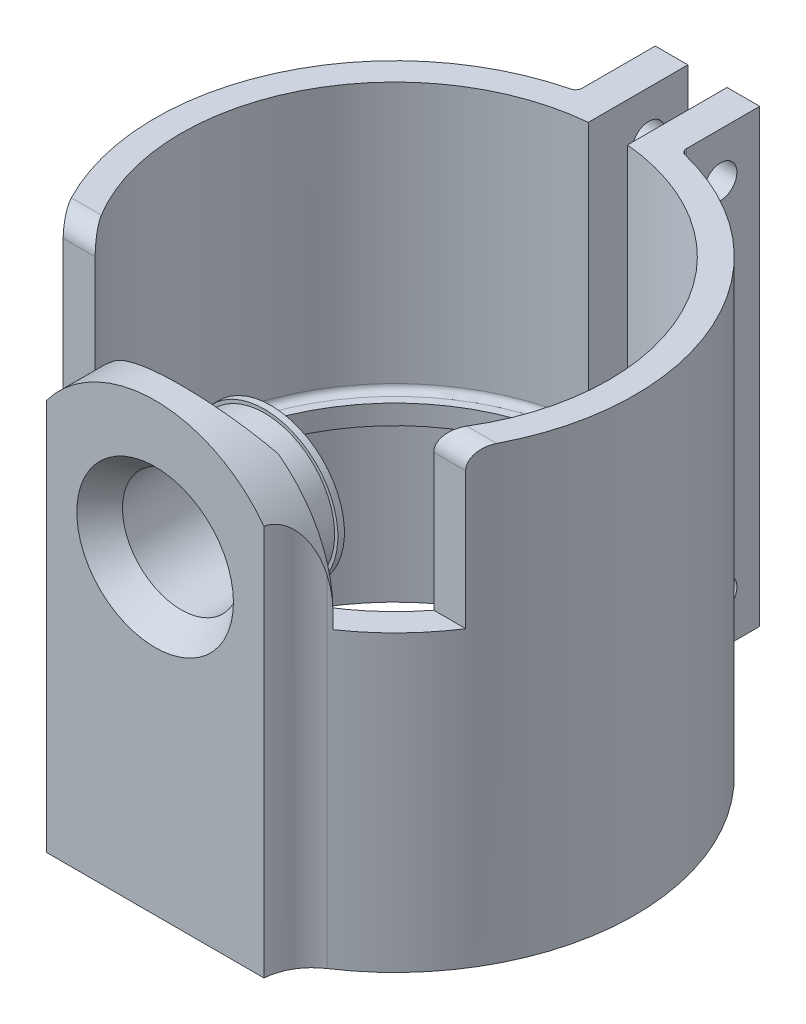
SolidWorks part; units mm, degrees
ref_plane "Спереди" through (0, 0, 0) normal (0, 0, 1) x (1, 0, 0)
ref_plane "Сверху" through (0, 0, 0) normal (0, 1, 0) x (1, 0, 0)
ref_plane "Справа" through (0, 0, 0) normal (1, 0, 0) x (0, 0, -1)
sketch "Эскиз1" plane through (0, 0, 0) normal (0, 1, 0) x (1, 0, 0)
  line L0 (0, 0) -> (0, -43.0119) construction
  line L2 (-16.6733, -36.75) -> (16.6733, -36.75)
  line L3 (-16.6733, -36.75) -> (-16.6733, -32.75)
  line L5 (16.6733, -36.75) -> (16.6733, -32.75)
  arc A0 (-16.6733, -32.75) -> (16.6733, -32.75) centre (0, 0) cw
  circle A1 centre (0, 0) radius 32.75
  dimension "D1" = 65.5
  dimension "D2" = 36.75
  dimension "D3" = 4
extrude "main" add sketch "Эскиз1" along normal blind 44 and the other way blind 25
sketch "Эскиз2" plane through (0, 0, 0) normal (0, 0, 1) x (1, 0, 0)
  circle A0 centre (0, 22.5) radius 11
  dimension "D1" = 22
  dimension "D2" = 22.5
extrude "hole" cut sketch "Эскиз2" along normal through all
sketch "Эскиз3" plane through (0, 0, 0) normal (0, 1, 0) x (1, 0, 0)
  circle A0 centre (0, 0) radius 32.75
  circle A1 centre (0, 0) radius 30.5
  circle A3 centre (0, 0) radius 32.75 construction
  dimension "D1" = 61
extrude "stop" add sketch "Эскиз3" along normal blind 3
sketch "Эскиз4" plane through (0, 0, 0) normal (0, 1, 0) x (1, 0, 0)
  line L0 (8, 35.8687) -> (0, 0) construction
  line L1 (0, 0) -> (-8, 35.8687) construction
  line L2 (0, 0) -> (0, 39.0687) construction
  line L3 (-8, 35.8687) -> (-8, 47.8687)
  line L4 (-8, 47.8687) -> (8, 47.8687)
  line L5 (8, 47.8687) -> (8, 35.8687)
  arc A0 (-8, 35.8687) -> (8, 35.8687) centre (0, 0) cw
  arc A1 (16.6733, -32.75) -> (-16.6733, -32.75) centre (0, 0) ccw construction
  dimension "D1" = 8
  dimension "D2" = 8
  dimension "D3" = 12
extrude "lock" add sketch "Эскиз4" against normal up to surface (25 mm away) and the other way up to surface (44 mm away) up to face at (0, -25, 32.75) other way up to face at (0, 44, 17.375)
sketch "Эскиз5" plane through (0, 0, 0) normal (0, 1, 0) x (1, 0, 0)
  line L0 (8, 47.8687) -> (-8, 47.8687) construction
  line L1 (-3, 0) -> (3, 0)
  line L2 (-3, 0) -> (-3, 47.8687)
  line L3 (-3, 47.8687) -> (3, 47.8687)
  line L4 (3, 0) -> (3, 47.8687)
  dimension "D1" = 3
extrude "slot" cut sketch "Эскиз5" against normal through all and the other way through all
sketch "Эскиз6" plane through (8, 0, 0) normal (1, 0, 0) x (0, 0, -1)
  line L0 (41.8687, 7.5457) -> (41.8687, -34.4595) construction
  line L1 (47.8687, -25) -> (35.8687, -25) construction
  line L3 (35.8687, 44) -> (47.8687, 44) construction
  circle A0 centre (41.8687, 37) radius 2.5
  circle A1 centre (41.8687, -18) radius 2.5
  point P4 (41.8687, -25)
  dimension "D1" = 7
  dimension "D2" = 5
  dimension "D3" = 7
extrude "small holes" cut sketch "Эскиз6" against normal through all
ref_plane "Плоскость1" through (0, 0, 20) normal (0, 0, 1) x (1, 0, 0)
sketch "Эскиз10" plane through (0, 0, 0) normal (1, 0, 0) x (0, 0, -1)
  line L0 (-20, 40.425) -> (-20, -40.425) construction
  line L1 (-20, 20.0487) -> (-30.3, 20.0487)
  line L2 (-20, 20.0487) -> (-20, 60)
  line L3 (-20, 60) -> (-30.3, 60)
  line L4 (-30.3, 20.0487) -> (-30.3, 60)
  dimension "D1" = 10.3
extrude "key slot" cut sketch "Эскиз10" against normal through all and the other way through all
sketch "Эскиз9" plane through (0, 0, 20) normal (0, 0, 1) x (1, 0, 0)
  circle A0 centre (0, 22.5) radius 9
  circle A1 centre (0, 22.5) radius 11
  dimension "D2" = 18
  dimension "D3" = 22
  dimension "D1" = 22.5
extrude "tube" add sketch "Эскиз9" along normal up to surface (16.75 mm away) up to face at (0, 9.5, 36.75)
sketch "Эскиз11" plane through (0, 0, 20) normal (0, 0, -1) x (-1, 0, 0)
  circle A0 centre (0, 22.5) radius 13
  circle A2 centre (0, 22.5) radius 10.75
  circle A3 centre (0, 22.5) radius 9 construction
  dimension "D1" = 21.5
  dimension "D2" = 26
extrude "tube slot" cut sketch "Эскиз11" against normal up to surface (10.3 mm away) up to face at (-16.6123, 32.0244, 30.3)
chamfer "Фаска1" distance 3 distance2 4 1 edges at (9, 22.5, 36.75) first distance on face at (0, 9.5, 36.75)
sketch "Эскиз12" plane through (0, 0, 20) normal (0, 0, -1) x (-1, 0, 0)
  circle A0 centre (0, 22.5) radius 11.25
  circle A1 centre (0, 22.5) radius 9
  circle A2 centre (0, 22.5) radius 9 construction
  dimension "D1" = 22.5
extrude "tube stop" add sketch "Эскиз12" along normal blind 1
sketch "Эскиз14" plane through (0, 0, 20) normal (0, 0, 1) x (1, 0, 0)
  line L2 (-20.796, 22.5) -> (-20.796, 44)
  line L3 (-20.796, 44) -> (20.796, 44)
  line L4 (20.796, 44) -> (20.796, 22.5)
  arc A0 (-20.796, 22.5) -> (20.796, 22.5) centre (0, 22.5) cw
  circle A2 centre (0, 22.5) radius 11 construction
extrude "tube external" cut sketch "Эскиз14" along normal through all
fillet "Скругление3" radius 8 2 edges at (-16.6733, 4.9643, 32.75) (16.6733, 4.9643, 32.75)
fillet "Скругление5" radius 1 1 edges at (0, 3, 32.75)
fillet "Скругление6" radius 1 2 edges at (8, 9.5, -35.8687) (-8, 9.5, -35.8687)
fillet "Скругление7" radius 3 2 edges at (28.3825, 44, 20) (-28.3825, 44, 20)
